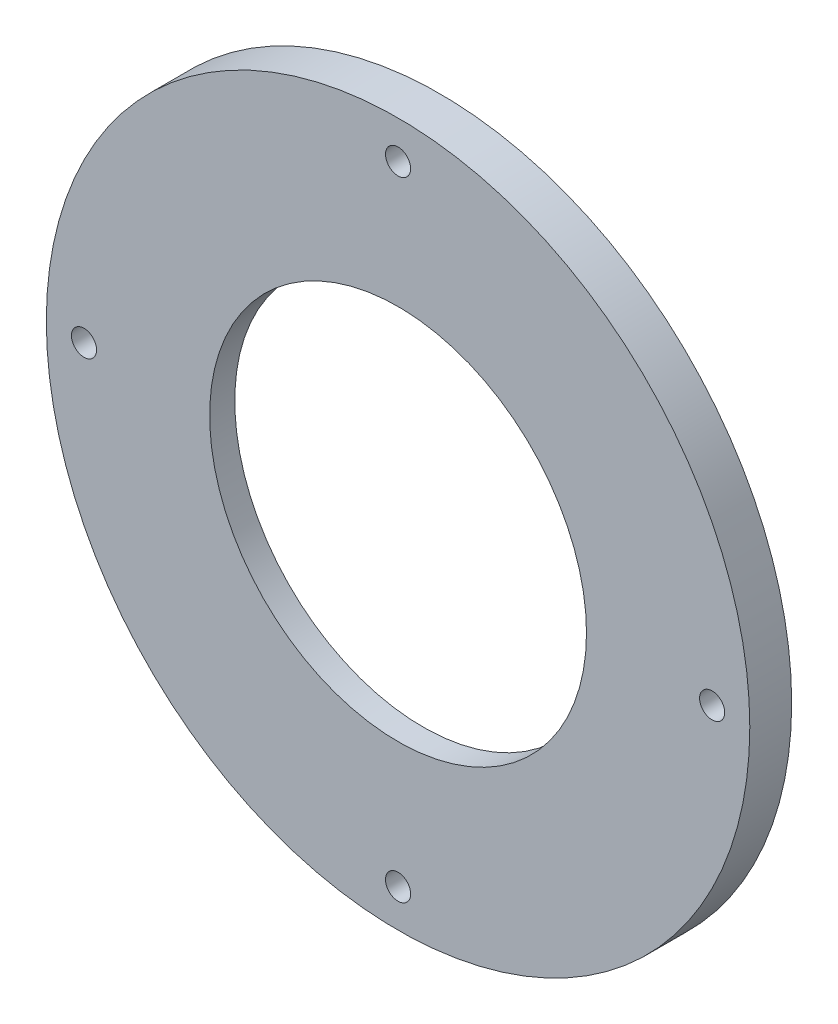
SolidWorks part; units mm, degrees
ref_plane "前视基准面" through (0, 0, 0) normal (0, 0, 1) x (1, 0, 0)
ref_plane "上视基准面" through (0, 0, 0) normal (0, 1, 0) x (1, 0, 0)
ref_plane "右视基准面" through (0, 0, 0) normal (1, 0, 0) x (0, 0, -1)
sketch "草图1" plane through (0, 0, 0) normal (0, 0, 1) x (1, 0, 0)
  line L0 (0, 62.5588) -> (0, -63.6272) construction
  line L1 (-59.9012, 0) -> (91.7255, 0) construction
  circle A0 centre (0, 0) radius 42
  circle A1 centre (0, 0) radius 37.5 construction
  circle A2 centre (0, 37.5) radius 1.5
  circle A3 centre (-37.5, 0) radius 1.5
  circle A4 centre (37.5, 0) radius 1.5
  circle A5 centre (0, 0) radius 22.5
  circle A6 centre (0, 0) radius 32.6
  circle A7 centre (0, -37.5) radius 1.5
  point P22 (0, 0)
  dimension "D1" = 84
  dimension "D2" = 65.2
  dimension "D3" = 45
  dimension "D4" = 75
  dimension "D5" = 3
  dimension "D6" = 3
  dimension "D7" = 3
  dimension "D8" = 3
extrude "凸台-拉伸1" add sketch "草图1" along normal blind 5 contours A0 A7 A6 A4 A3 A2 | A6 A5
extrude "切除-拉伸1" cut sketch "草图1<4>" along normal blind 2 contours A6
sketch "草图1<4>" plane through (0, 0, 0) normal (0, 0, 1) x (1, 0, 0) same geometry as "草图1"
